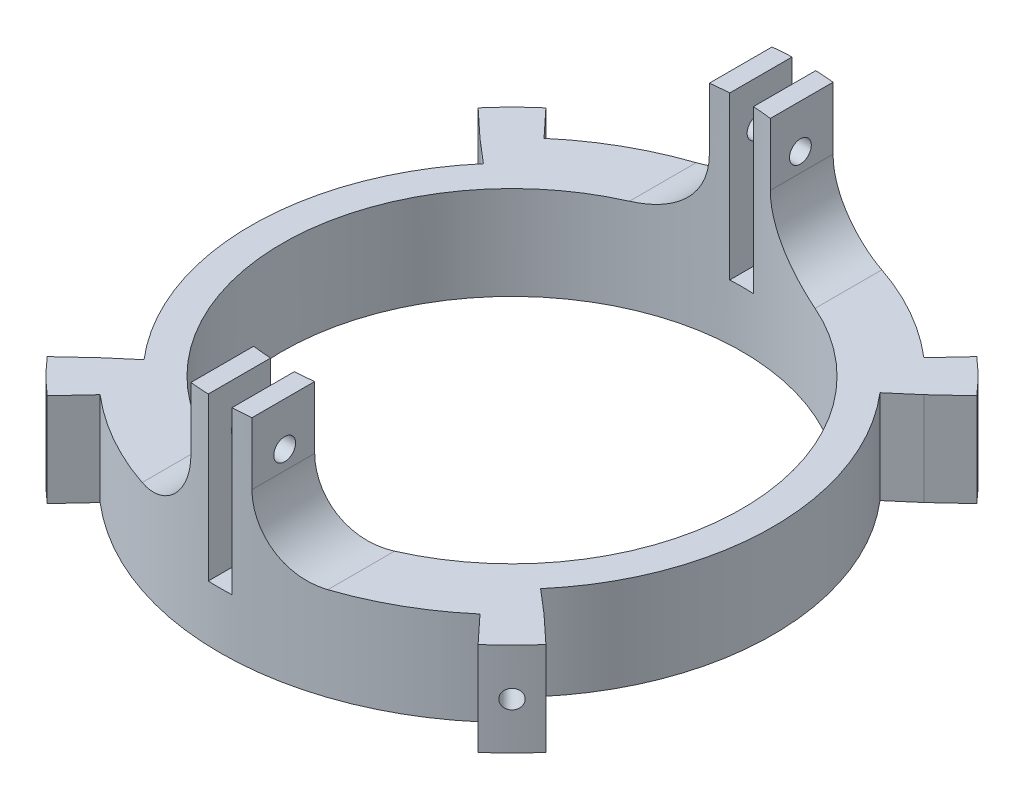
SolidWorks part; units mm, degrees
note: '?' marks a value the reader was unsure of.
ref_plane "Front Plane" through (0, 0, 0) normal (0, 0, 1) x (1, 0, 0)
ref_plane "Top Plane" through (0, 0, 0) normal (0, 1, 0) x (1, 0, 0)
ref_plane "Right Plane" through (0, 0, 0) normal (1, 0, 0) x (0, 0, -1)
sketch "Sketch1" plane through (0, 0, 0) normal (0, 1, 0) x (1, 0, 0)
  line L0 (-97.4451, 0) -> (50.4854, 0) construction
  circle A0 centre (0, 0) radius 36.9
  circle A2 centre (0, 0) radius 46.9
  dimension "D1" = 73.8
  dimension "D2" = 10
extrude "Boss-Extrude1" add sketch "Sketch1" along normal blind 15
sketch "Sketch7" plane through (0, 15, 0) normal (0, 1, 0) x (1, 0, 0)
  line L0 (0, 46.9) -> (0, -46.9) construction
  line L1 (-46.9, 0) -> (46.9, 0) construction
  line L2 (-1.9, 46.8615) -> (-1.9, 36.8511)
  line L3 (-4.9, 46.6433) -> (-4.9, 36.5732)
  line L4 (4.9, 46.6433) -> (4.9, 36.5732)
  line L5 (1.9, 46.8615) -> (1.9, 36.8511)
  line L6 (1.9, -46.8615) -> (1.9, -36.8511)
  line L7 (4.9, -46.6433) -> (4.9, -36.5732)
  line L8 (-4.9, -46.6433) -> (-4.9, -36.5732)
  line L9 (-1.9, -46.8615) -> (-1.9, -36.8511)
  circle A0 centre (0, 0) radius 46.9 construction
  circle A1 centre (0, 0) radius 36.9 construction
  arc A4 (-1.9, 46.8615) -> (-4.9, 46.6433) centre (0, 0) ccw
  arc A5 (-1.9, 36.8511) -> (-4.9, 36.5732) centre (0, 0) ccw
  arc A6 (1.9, 36.8511) -> (4.9, 36.5732) centre (0, 0) cw
  arc A7 (1.9, 46.8615) -> (4.9, 46.6433) centre (0, 0) cw
  arc A8 (1.9, -46.8615) -> (4.9, -46.6433) centre (0, 0) ccw
  arc A9 (1.9, -36.8511) -> (4.9, -36.5732) centre (0, 0) ccw
  arc A10 (-1.9, -36.8511) -> (-4.9, -36.5732) centre (0, 0) cw
  arc A11 (-1.9, -46.8615) -> (-4.9, -46.6433) centre (0, 0) cw
  dimension "D1" = 3
  dimension "D2" = 1.9
extrude "Boss-Extrude2" add sketch "Sketch7" along normal blind 20
sketch "Sketch4" plane through (0, 15, 0) normal (0, 1, 0) x (1, 0, 0)
  line L8 (-46.9, 0) -> (46.9, 0) construction
  line L9 (-1.9, 49.1774) -> (1.9, 49.1774)
  line L10 (-1.9, 49.1774) -> (-1.9, 35.5049)
  line L11 (-1.9, 35.5049) -> (1.9, 35.5049)
  line L12 (1.9, 49.1774) -> (1.9, 35.5049)
  line L13 (1.9, -49.1774) -> (1.9, -35.5049)
  line L14 (-1.9, -35.5049) -> (1.9, -35.5049)
  line L15 (-1.9, -49.1774) -> (-1.9, -35.5049)
  line L16 (-1.9, -49.1774) -> (1.9, -49.1774)
  arc A8 (-4.9, 46.6433) -> (-4.9, -46.6433) centre (0, 0) ccw construction
  arc A9 (4.9, -46.6433) -> (4.9, 46.6433) centre (0, 0) ccw construction
extrude "Cut-Extrude2" cut sketch "Sketch4" against normal blind 6
sketch "Sketch5" plane through (0, 0, 0) normal (1, 0, 0) x (0, 0, -1)
  line L0 (0, 0) -> (0, 45.4601) construction
  line L1 (-48.739, 28) -> (49.7163, 28) construction
  line L2 (-41.4, 41.9757) -> (-41.4, -3.4488) construction
  circle A0 centre (-41.4, 28) radius 1.75
  dimension "D2" = 3.5
  dimension "D1" = 41.4
  dimension "D3" = 28
extrude "Cut-Extrude3" cut sketch "Sketch5" against normal through all both and the other way through all
mirror "Mirror1" about plane through (0, 0, 0) normal (0, 0, 1) of "Cut-Extrude3"
fillet "Fillet3" radius 10 4 edges at (4.9, 15, -41.6083) (-4.9, 15, -41.6083) (-4.9, 15, 41.6083) (4.9, 15, 41.6083)
sketch "Sketch8" plane through (0, 0, 0) normal (0, -1, 0) x (1, 0, 0)
  line L0 (0, 0) -> (-42.0707, 42.0707) construction
  line L1 (-35.6326, 30.4947) -> (-40.0274, 34.5864)
  line L2 (-30.4947, 35.6326) -> (-34.5864, 40.0274)
  circle A1 centre (0, 0) radius 52.9 construction
  circle A2 centre (0, 0) radius 46.9 construction
  arc A3 (-34.5864, 40.0274) -> (-40.0309, 34.5824) centre (0, 0) ccw
  arc A4 (-30.4947, 35.6326) -> (-35.6326, 30.4947) centre (0, 0) ccw
  dimension "D1" = 105.8
extrude "Boss-Extrude3" add sketch "Sketch8" against normal blind 15 contours L2 A3 L1 L0
ref_plane "Plane1" through (-37.4059, 0, 37.4059) normal (-0.7071, 0, 0.7071) x (0, -1, 0)
sketch "Sketch9" plane through (-37.4059, 0, 37.4059) normal (-0.7071, 0, 0.7071) x (0, -1, 0)
  line L0 (-15, 0) -> (0, 0) construction
  line L1 (-15, 3.8473) -> (-15, -3.8473) construction
  circle A0 centre (-7.5, 0) radius 1.5
  dimension "D1" = 3
extrude "Cut-Extrude4" cut sketch "Sketch9" against normal blind 15
ref_axis "Axis1" through (0, 35, 0) along (0, -1, 0)?
pattern_circular "CirPattern1" count 4 over 360 about axis through (0, 0, 0) along (0, 1, 0) of "Boss-Extrude3", "Cut-Extrude4"
sketch "Sketch10" plane through (0, 0, 0) normal (0, -1, 0) x (1, 0, 0)
  line L0 (-35.6326, 30.4947) -> (-31.8338, 27.2437)
  line L1 (-35.6326, -30.4947) -> (-31.8338, -27.2437)
  line L2 (0, 46.9) -> (0, -46.9) construction
  line L3 (35.6326, -30.4947) -> (31.8338, -27.2437)
  line L4 (35.6326, 30.4947) -> (31.8338, 27.2437)
  arc A1 (-35.6326, 30.4947) -> (-35.6326, -30.4947) centre (0, 0) ccw construction
  arc A2 (-35.6326, 30.4947) -> (-35.6326, -30.4947) centre (0, 0) ccw
  arc A3 (-31.8338, 27.2437) -> (-31.8338, -27.2437) centre (0, 0) ccw
  arc A4 (30.4947, 35.6326) -> (-30.4947, 35.6326) centre (0, 0) ccw construction
  arc A5 (-30.4947, -35.6326) -> (30.4947, -35.6326) centre (0, 0) ccw construction
  arc A6 (31.8338, 27.2437) -> (31.8338, -27.2437) centre (0, 0) cw
  arc A7 (35.6326, 30.4947) -> (35.6326, -30.4947) centre (0, 0) cw
  dimension "D1" = 5
extrude "Cut-Extrude5" cut sketch "Sketch10" against normal blind 15
